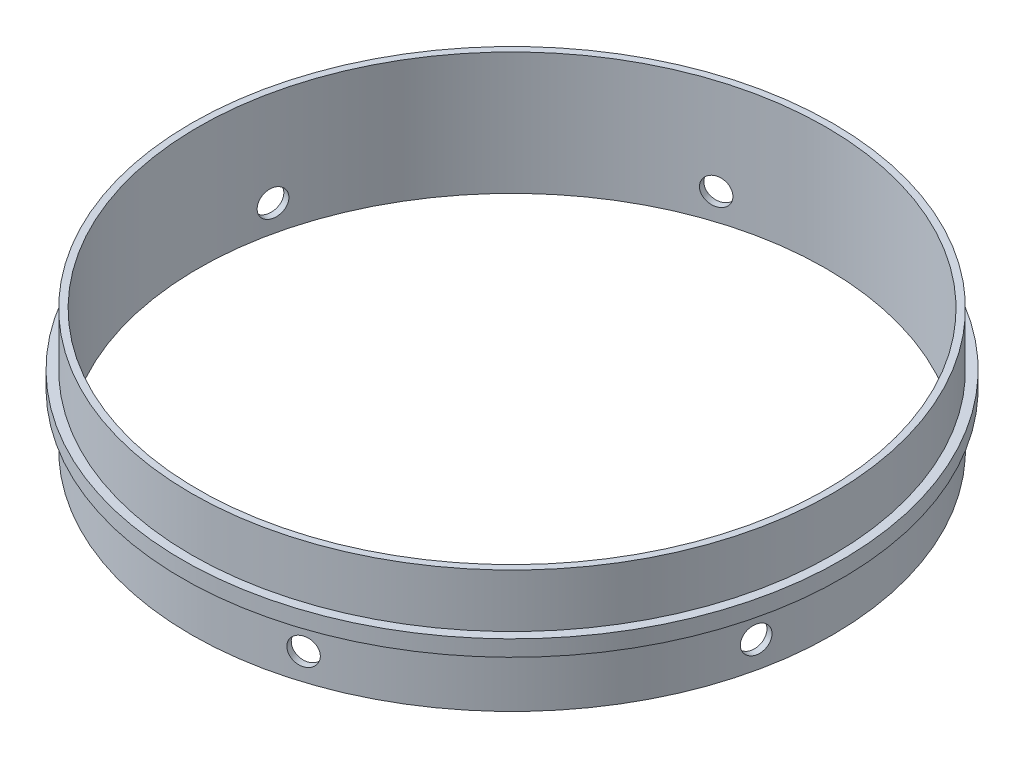
SolidWorks part; units mm, degrees
material "6061-T6 (SS)"
ref_plane "Front Plane" through (0, 0, 0) normal (0, 0, 1) x (1, 0, 0)
ref_plane "Top Plane" through (0, 0, 0) normal (0, 1, 0) x (1, 0, 0)
ref_plane "Right Plane" through (0, 0, 0) normal (1, 0, 0) x (0, 0, -1)
ref_axis "Axis1" through (0, -55, 0) along (0, 1, 0)
sketch "Sketch1" plane through (0, 0, 0) normal (0, 0, 1) x (1, 0, 0)
  line L0 (74.8665, 0) -> (74.8665, 29.21)
  line L1 (74.8665, 29.21) -> (76.454, 29.21)
  line L2 (76.454, 29.21) -> (76.454, 16.51)
  line L3 (76.454, 16.51) -> (78.5876, 16.51)
  line L4 (78.5876, 16.51) -> (78.5876, 12.7)
  line L5 (78.5876, 12.7) -> (76.454, 12.7)
  line L6 (76.454, 12.7) -> (76.454, 0)
  line L7 (76.454, 0) -> (74.8665, 0)
  line L8 (0, -55) -> (0, 55) construction
  line L9 (55, 0) -> (-55, 0) construction
  dimension "D1" = 1.5875
  dimension "D2" = 76.454
  dimension "D3" = 12.7
  dimension "D4" = 3.81
  dimension "D5" = 12.7
  dimension "D6" = 78.5876
revolve "Revolve1" add sketch "Sketch1" angle 360 about axis through (0, -55, 0) along (0, 1, 0)
hole_wizard "1/4 (0.25) Diameter Hole1" positions "3DSketch1" profile "Sketch2" hole size "1/4" standard "ANSI Inch" end condition up to next
sketch3d "3DSketch1"
  point P0 (23.1229, 6.35, 72.8735)
  dimension "D1" = 6.35
sketch "Sketch2" plane through (23.1229, 6.35, 72.8735) normal (0, 1, 0) x (0.9532, 0, -0.3024)
  line L0 (0, 0) -> (0, 182.2233)
  line L1 (0, 182.2233) -> (3.175, 182.2233)
  line L2 (3.175, 182.2233) -> (3.175, 0)
  line L5 (3.175, 0) -> (0, 0)
  line L11 (0, -6.35) -> (0, 107.95) construction
  dimension "Thru Hole Dia." = 6.35
  dimension "Thru Hole Depth" = 182.2233
pattern_circular "CirPattern1" count 6 over 360 about axis through (0, -55, 0) along (0, 1, 0) of "1/4 (0.25) Diameter Hole1"
